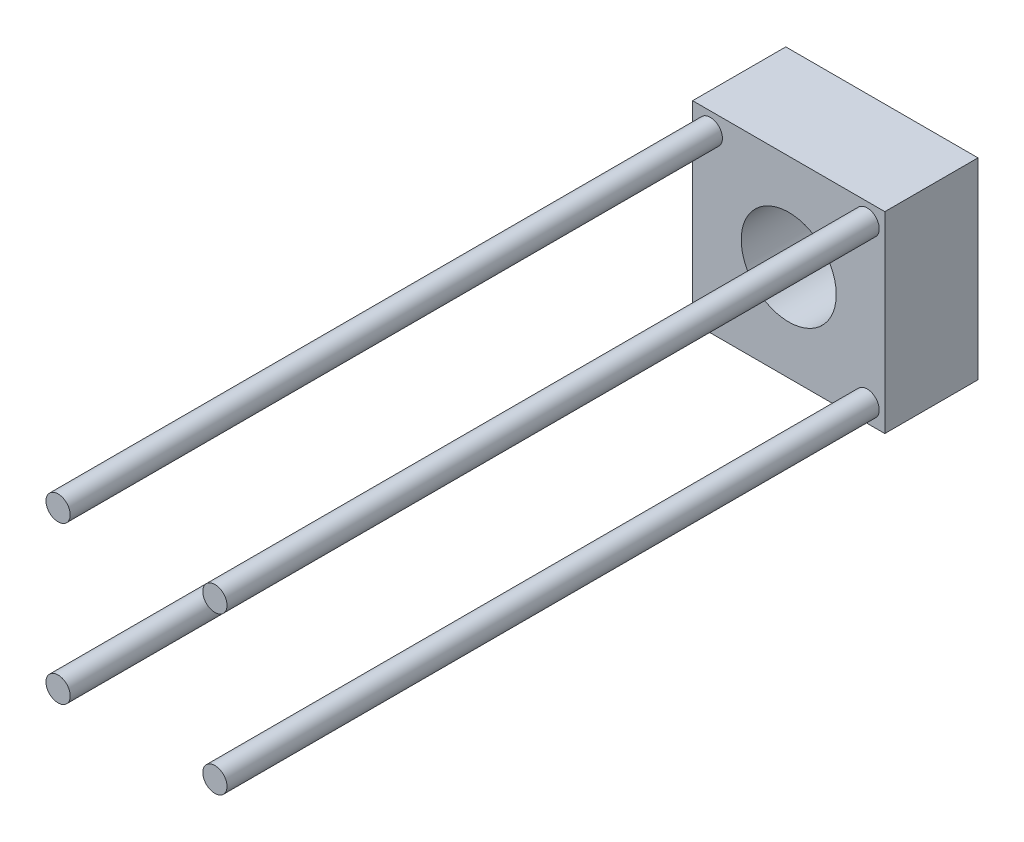
SolidWorks part; units mm, degrees
ref_plane "xy_plane" through (0, 0, 0) normal (0, 0, 1) x (1, 0, 0)
ref_plane "zx_plane" through (0, 0, 0) normal (0, 1, 0) x (1, 0, 0)
ref_plane "yz_plane" through (0, 0, 0) normal (1, 0, 0) x (0, 0, -1)
ref_axis "x_axis" through (-80.9, 0, 0) along (1, 0, 0)
ref_axis "y_axis" through (0, -50, 0) along (0, 1, 0)
ref_axis "z_axis" through (0, 0, -80.9) along (0, 0, 1)
ref_plane "xMid_plane" through (0, 0, 0) normal (1, 0, 0) x (0, 0, -1)
ref_plane "xMin_plane" through (-5.1573, 0, 0) normal (1, 0, 0) x (0, 0, -1)
ref_plane "xMax_plane" through (5.1573, 0, 0) normal (1, 0, 0) x (0, 0, -1)
ref_plane "yMid_plane" through (0, 0, 0) normal (0, 1, 0) x (1, 0, 0)
ref_plane "yMin_plane" through (0, -5.1573, 0) normal (0, 1, 0) x (1, 0, 0)
ref_plane "yMax_plane" through (0, 5.1573, 0) normal (0, 1, 0) x (1, 0, 0)
ref_plane "zMid_plane" through (0, 0, 0) normal (0, 0, 1) x (1, 0, 0)
ref_plane "zMin_plane" through (0, 0, -20) normal (0, 0, 1) x (1, 0, 0)
ref_plane "zMax_plane" through (0, 0, 20) normal (0, 0, 1) x (1, 0, 0)
sketch "projectionXy_sketch" plane through (0, 0, 0) normal (0, 0, 1) x (1, 0, 0)
  line L0 (55, 5.1573) -> (-55, 5.1573) construction
  line L1 (-5.1573, 5.1573) -> (5.1573, 5.1573)
  line L2 (-5.1573, 5.1573) -> (-5.1573, -5.1573)
  line L3 (-5.1573, -5.1573) -> (5.1573, -5.1573)
  line L4 (5.1573, 5.1573) -> (5.1573, -5.1573)
  line L5 (55, -5.1573) -> (-55, -5.1573) construction
  line L6 (5.1573, -55) -> (5.1573, 55) construction
  line L7 (-5.1573, -55) -> (-5.1573, 55) construction
extrude "mainBody_extrude" add sketch "projectionXy_sketch" along normal blind 5 from surface starting at plane "zMin_plane"
sketch "bore_sketch" plane through (0, 0, 0) normal (0, 0, 1) x (1, 0, 0)
  circle A0 centre (0, 0) radius 2.55
  dimension "D1" = 5.1
extrude "bore_cut" cut sketch "bore_sketch" against normal through all both and the other way through all from surface starting at plane "zMid_plane"
sketch "posts_sketch" plane through (0, 0, 0) normal (0, 0, 1) x (1, 0, 0)
  line L0 (0, 0) -> (4.2073, -4.2073) construction
  line L1 (-80.9, 0) -> (80.9, 0) construction
  circle A0 centre (4.2073, -4.2073) radius 0.65
  circle A1 centre (-4.2073, -4.2073) radius 0.65
  circle A2 centre (-4.2073, 4.2073) radius 0.65
  circle A3 centre (4.2073, 4.2073) radius 0.65
  dimension "D1" = 1.3
  dimension "D3" = 5.95
  dimension "D4" = 45
  dimension "D2" = 4
extrude "posts_extrude" add sketch "posts_sketch" along normal up to surface (20 mm away) from surface up to plane "zMax_plane" starting at plane "zMin_plane"
equation "\"D1@xMin_plane\"= \"externalParameters.this.extentX\" / 2"
equation "\"D1@xMax_plane\" = \"externalParameters.this.extentX\" / 2"
equation "\"D1@yMin_plane\" = \"externalParameters.this.extentY\" / 2"
equation "\"D1@yMax_plane\" = \"externalParameters.this.extentY\" / 2"
equation "\"D1@zMin_plane\"= \"externalParameters.this.extentZ\" / 2"
equation "\"D1@zMax_plane\" = \"externalParameters.this.extentZ\" / 2"
equation "\"D1@mainBody_extrude\" = \"externalParameters.this.base.extentZ\""
equation "\"D1@posts_sketch\"=\"externalParameters.this.post.diameter\""
equation "\"D4@posts_sketch\"=45deg"
equation "\"D3@posts_sketch\"=\"externalParameters.this.posts.pattern.radius\""
